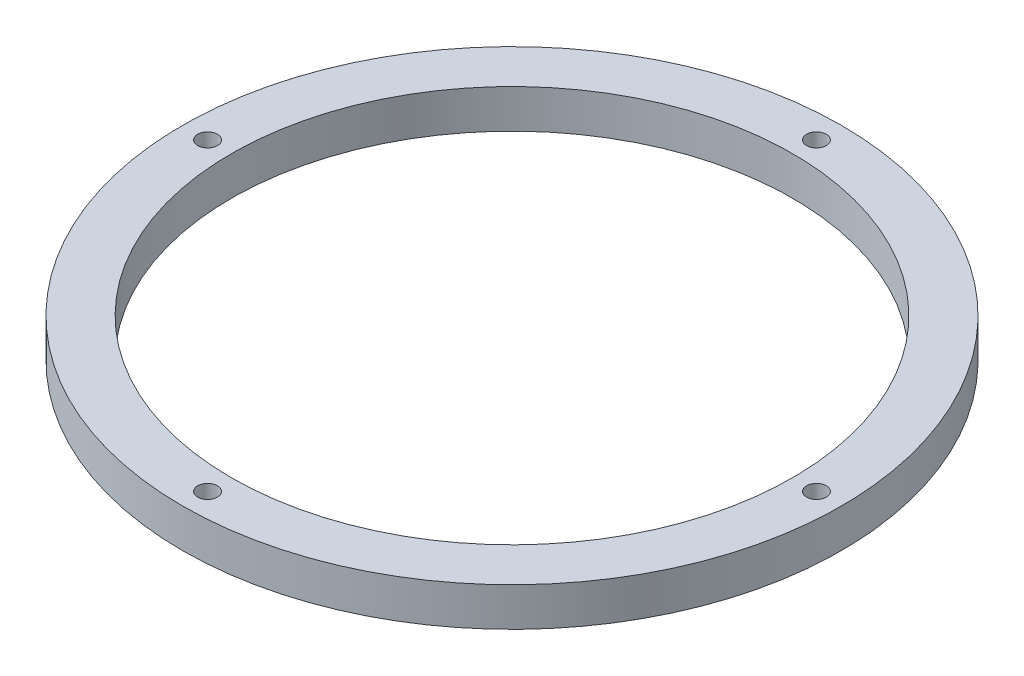
SolidWorks part; units mm, degrees
ref_plane "Front Plane" through (0, 0, 0) normal (0, 0, 1) x (1, 0, 0)
ref_plane "Top Plane" through (0, 0, 0) normal (0, 1, 0) x (1, 0, 0)
ref_plane "Right Plane" through (0, 0, 0) normal (1, 0, 0) x (0, 0, -1)
sketch "Sketch1" plane through (0, 0, 0) normal (0, 1, 0) x (1, 0, 0)
  circle A0 centre (0, 0) radius 85.25
  circle A5 centre (0, 0) radius 72.6
  dimension "D1" = 170.5
  dimension "D2" = 145.2
extrude "Boss-Extrude1" add sketch "Sketch1" along normal mid plane 10
sketch "Sketch2" plane through (0, 0, 0) normal (0, 1, 0) x (1, 0, 0)
  circle A0 centre (-78.75, 0) radius 1.27
  dimension "D2" = 2.54
  dimension "D1" = 78.75
extrude "Cut-Extrude1" cut sketch "Sketch2" against normal through all both and the other way through all
ref_axis "Axis1" through (0, 5.5, 0) along (0, -1, 0)
pattern_circular "CirPattern1" count 4 over 360 about axis through (0, 5.5, 0) along (0, -1, 0) of "Cut-Extrude1"
hole_wizard "CSK for #10 Flat Head Machine Screw (100)1" positions "3DSketch1" profile "Sketch3" countersink size "#10" standard "ANSI Inch" end condition through all
sketch3d "3DSketch1"
  line L0 (78.75, -5, 0) -> (78.75, 5, 0) construction
  line L1 (0, -5, -78.75) -> (0, 5, -78.75) construction
  line L2 (-78.75, -5, 0) -> (-78.75, 5, 0) construction
  line L3 (0, -5, 78.75) -> (0, 5, 78.75) construction
  point P0 (78.75, -5, 0)
  point P4 (0, -5, -78.75)
  point P8 (-78.75, -5, 0)
  point P12 (0, -5, 78.75)
sketch "Sketch3" plane through (78.75, -5, 0) normal (1, 0, 0) x (0, 0, -1)
  line L0 (0, 0) -> (0, 10)
  line L1 (0, 10) -> (2.5527, 10)
  line L2 (2.5527, 10) -> (2.5527, 1.9608)
  line L3 (2.5527, 1.9608) -> (4.8895, 0)
  line L5 (4.8895, 0) -> (0, 0)
  line L6 (-2.5527, 1.9608) -> (-4.8895, 0) construction
  line L11 (0, -6.35) -> (0, 107.95) construction
  dimension "Thru Hole Dia." = 5.1054
  dimension "Thru Hole Depth" = 10
  dimension "Near C'Sink Dia." = 9.779
  dimension "Near C'Sink Angle" = 100
equation "\"thicknes\"= 10mm"
equation "\"D1@Boss-Extrude1\"=\"thicknes\""
equation "\"id\"= 145.2mm"
equation "\"D2@Sketch1\"=\"id\""
equation "\"od\"= 170.5mm"
equation "\"D1@Sketch1\"=\"od\""
equation "\"hole_radius\"= \"hole_diameter\" / 2"
equation "\"D1@Sketch2\"=\"hole_radius\""
equation "\"hole_diameter\"= 157.5mm"
